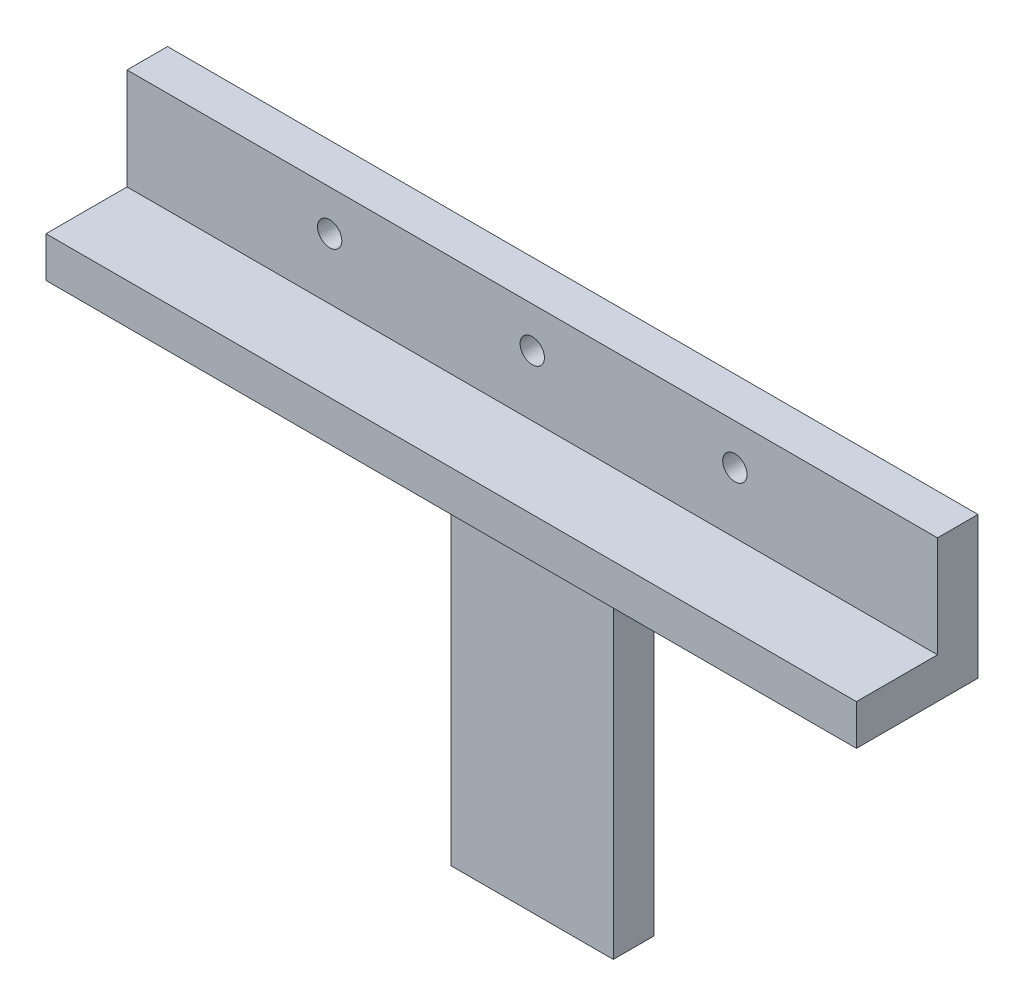
SolidWorks part; units mm, degrees
ref_plane "前基準面" through (0, 0, 0) normal (0, 0, 1) x (1, 0, 0)
ref_plane "上基準面" through (0, 0, 0) normal (0, 1, 0) x (1, 0, 0)
ref_plane "右基準面" through (0, 0, 0) normal (1, 0, 0) x (0, 0, -1)
sketch "草圖1" plane through (0, 0, 0) normal (0, 0, 1) x (1, 0, 0)
  line L0 (-40.1551, 7.2196) -> (-80.1551, 7.2196)
  line L1 (-80.1551, 7.2196) -> (-80.1551, 112.3297)
  line L2 (-80.1551, 112.3297) -> (-160.1551, 112.3297)
  line L3 (-160.1551, 112.3297) -> (-160.1551, 137.3297)
  line L4 (-160.1551, 137.3297) -> (39.8449, 137.3297)
  line L5 (39.8449, 137.3297) -> (39.8449, 112.3297)
  line L6 (39.8449, 112.3297) -> (-40.1551, 112.3297)
  line L7 (-40.1551, 112.3297) -> (-40.1551, 7.2196)
  line L8 (-60.1551, 137.3297) -> (-60.1551, 151.4898) construction
  line L9 (-60.1551, 7.2196) -> (-60.1551, -12.7977) construction
  dimension "D1" = 200
  dimension "D2" = 25
  dimension "D3" = 40
extrude "填料-伸長1" add sketch "草圖1" along normal blind 10
sketch "Sketch2" plane through (0, 112.3297, 0) normal (0, -1, 0) x (1, 0, 0)
  line L1 (39.8449, 0) -> (-160.1551, 0)
  line L2 (39.8449, 0) -> (39.8449, 30)
  line L3 (39.8449, 30) -> (-160.1551, 30)
  line L4 (-160.1551, 0) -> (-160.1551, 30)
  line L5 (-40.1551, 10) -> (39.8449, 10) construction
  point P5 (0, 0)
  point P7 (-160.1551, 0)
  point P8 (39.8449, 0)
  dimension "D1" = 20
extrude "Boss-Extrude1" add sketch "Sketch2" along normal blind 10
sketch "草圖2" plane through (0, 0, 10) normal (0, 0, 1) x (1, 0, 0)
  line L0 (39.8449, 112.3297) -> (39.8449, 137.3297) construction
  line L2 (-160.1551, 112.3297) -> (39.8449, 112.3297) construction
  circle A0 centre (-10.1551, 127.3297) radius 3
  dimension "D1" = 6
  dimension "D2" = 15
  dimension "D6" = 50
extrude "除料-伸長1" cut sketch "草圖2" against normal up to surface (10 mm away) up to face at (-60.1551, 87.3022, 0)
pattern_linear "LPattern1" count 3 spacing 50 along (-1, 0, 0) of "除料-伸長1"
